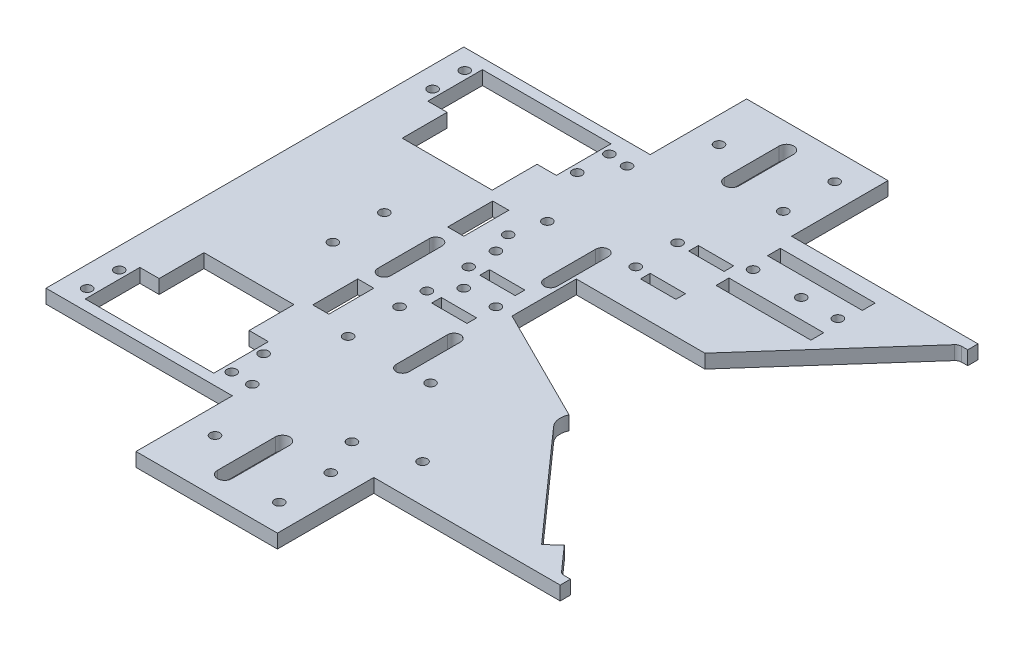
SolidWorks part; units mm, degrees
material "Acrylic (Medium-high impact)"
ref_plane "Front Plane" through (0, 0, 0) normal (0, 0, 1) x (1, 0, 0)
ref_plane "Top Plane" through (0, 0, 0) normal (0, 1, 0) x (1, 0, 0)
ref_plane "Right Plane" through (0, 0, 0) normal (1, 0, 0) x (0, 0, -1)
sketch "Sketch2" plane through (0, 0, 0) normal (0, 1, 0) x (1, 0, 0)
  line L2 (0, 0) -> (0, 65)
  line L3 (0, 65) -> (58, 65)
  line L4 (160, 0) -> (160, 65)
  line L8 (0, 0) -> (160, 0)
  line L9 (102, 65) -> (160, 65)
  line L11 (102, 65) -> (102, 95)
  line L12 (58, 65) -> (58, 95)
  line L13 (58, 95) -> (102, 95)
  dimension "D1" = 65
  dimension "D2" = 160
  dimension "D3" = 44
  dimension "D4" = 30
extrude "Boss-Extrude1" add sketch "Sketch2" along normal blind 4.3
mirror "Mirror1" about plane through (0, 4.3, 0) normal (0, 0, -1) of bodies 101
sketch "Sketch3" plane through (0, 4.3, 0) normal (0, 1, 0) x (1, 0, 0)
  line L0 (160, 61.8) -> (160, -61.8)
  line L1 (120.0126, 20) -> (157.1565, 61.8)
  line L3 (80.0126, 0) -> (80.0126, 20)
  line L4 (80.0126, 20) -> (120.0126, 20)
  line L12 (160, 65) -> (102, 65)
  line L13 (102, 65) -> (102, 95)
  line L15 (102, 95) -> (58, 95)
  line L16 (58, 65) -> (0, 65)
  line L17 (0, 65) -> (0, -65)
  line L18 (0, -65) -> (58, -65)
  line L20 (58, 95) -> (58, 65)
  line L22 (102, -65) -> (160, -65)
  line L23 (160, -65) -> (160, 65)
  line L36 (58, -65) -> (58, -95)
  line L38 (58, -95) -> (102, -95)
  line L39 (58, -95) -> (102, -95)
  line L40 (102, -95) -> (102, -65)
  line L42 (160, -61.8) -> (157.1556, -61.8)
  line L45 (160, 61.8) -> (157.1565, 61.8)
  line L48 (80.0126, 0) -> (120, -20)
  line L49 (120, -20) -> (157.1556, -61.8)
  line M24 (160, -65) -> (160, 65)
  dimension "D2" = 130
  dimension "D3" = 20
  dimension "D4" = 40
  dimension "D1" = 0
extrude "Cut-Extrude1" cut sketch "Sketch3" against normal blind 4.5 contours L48 L49 L1 L4 L3 M24 region at (132.7054, 4.3, -1.1594)
fillet "Fillet1" radius 2 2 edges at (157.1565, 2.15, -61.8) (157.1556, 2.15, 61.8)
ref_axis "Axis1" through (80, 4.3, 95) along (0, 0, -1)
sketch "Sketch4" plane through (0, 4.3, 0) normal (0, 1, 0) x (1, 0, 0)
  line L0 (80, -95) -> (80, 95)
  line L1 (102, -95) -> (58, -95) construction
  line L2 (102, 95) -> (58, 95) construction
ref_plane "Plane2" through (0, 4.3, 0) normal (0, 1, 0) x (1, 0, 0)
sketch "Sketch6" plane through (0, 4.3, 0) normal (0, 1, 0) x (1, 0, 0)
  line L3 (9, -61.8) -> (49, -61.8)
  line L6 (29, -45.8) -> (29, -44.8)
  line L7 (9, -44.8) -> (15, -44.8)
  line L11 (43, -44.8) -> (43, -30.8418)
  line L12 (15, -44.8) -> (15, -30.8418)
  line L13 (15, -30.8418) -> (43, -30.8418)
  line L15 (0, 0) -> (80.0126, 0)
  line L16 (80.0126, 0) -> (120, -20) construction
  line L18 (9, 44.8) -> (15, 44.8)
  line L20 (15, 30.8418) -> (43, 30.8418)
  line L21 (15, 44.8) -> (15, 30.8418)
  line L22 (43, 44.8) -> (43, 30.8418)
  line L25 (15, -45.8) -> (15, -30.8418) construction
  line L27 (9, 61.8) -> (49, 61.8)
  line L30 (4, -61.8) -> (3, -61.8)
  line L31 (0, -61.8) -> (160, -61.8) construction
  line L32 (3, -61.8) -> (4, -61.8)
  line L33 (3, -44.8) -> (3, -62.8) construction
  line L34 (3, -62.8) -> (55, -62.8) construction
  line L35 (55, -44.8) -> (55, -62.8) construction
  line L36 (4, -61.8) -> (54, -61.8) construction
  line L37 (0, 61.8) -> (160, 61.8) construction
  line L38 (54, 61.8) -> (55, 61.8)
  line L39 (54, 61.8) -> (55, 61.8)
  line L40 (43, 44.8) -> (49, 44.8)
  line L41 (4, -45.8) -> (4, -61.8) construction
  line L42 (4, -45.8) -> (54, -45.8) construction
  line L43 (43, -44.8) -> (49, -44.8)
  line L44 (3, -44.8) -> (55, -44.8) construction
  line L45 (29, -45.8) -> (29, -30.8418) construction
  line L46 (43, -45.8) -> (43, -30.8418) construction
  line L47 (54, -45.8) -> (54, -61.8) construction
  line L48 (9, -61.8) -> (49, -61.8)
  line L52 (9, 61.8) -> (9, 44.8)
  line L53 (55, 61.8) -> (54, 61.8)
  line L56 (49, 61.8) -> (49, 44.8)
  line L59 (3, -61.8) -> (4, -61.8)
  line L60 (9, -44.8) -> (9, -61.8)
  line L64 (49, -44.8) -> (49, -61.8)
  dimension "D4" = 1
  dimension "D5" = 14
  dimension "D6" = 14
extrude "Cut-Extrude2" cut sketch "Sketch6" against normal blind 10
sketch "Sketch8" plane through (0, 4.3, 0) normal (0, 1, 0) x (1, 0, 0)
  circle A0 centre (6.5, 58.8) radius 1.5
  circle A1 centre (6.5, 48.8) radius 1.5
  circle A2 centre (51.5, 48.8) radius 1.5
  circle A3 centre (51.5, 58.8) radius 1.5
  circle A4 centre (6.5, -48.7) radius 1.5
  circle A5 centre (6.5, -58.7) radius 1.5
  circle A6 centre (51.5, -58.7) radius 1.5
  circle A7 centre (51.5, -48.8) radius 1.5
  dimension "D7" = 3
extrude "Cut-Extrude3" cut sketch "Sketch8" against normal blind 10
sketch "Sketch9" plane through (0, 0, 0) normal (0, -1, 0) x (1, 0, 0)
  line L0 (75.75, 69.4) -> (75.75, 87.4)
  line L1 (75.75, -87.4) -> (75.75, -70.4)
  line L2 (80.25, -87.4) -> (80.25, -70.4)
  line L4 (80.25, 69.4) -> (80.25, 87.4)
  circle A0 centre (94, 70.4) radius 1.5
  circle A1 centre (66, 78.4) radius 1.5
  circle A2 centre (66, -78.4) radius 1.5
  circle A3 centre (94, -86.4) radius 1.5
  circle A4 centre (94, 86.4) radius 1.5
  circle A5 centre (94, -70.4) radius 1.5
  arc A6 (75.75, -87.4) -> (80.25, -87.4) centre (78, -87.4) ccw
  arc A7 (80.25, -70.4) -> (75.75, -70.4) centre (78, -70.4) ccw
  arc A10 (75.75, 69.4) -> (80.25, 69.4) centre (78, 69.4) ccw
  arc A12 (80.25, 87.4) -> (75.75, 87.4) centre (78, 87.4) ccw
  dimension "D1" = 3
extrude "Cut-Extrude4" cut sketch "Sketch9" against normal blind 10
sketch "Sketch7" plane through (0, 4.3, 0) normal (0, 1, 0) x (1, 0, 0)
  line L0 (0, 0) -> (80.0126, 0)
  line L1 (0, 65) -> (0, -65) construction
  line L2 (80.0126, 0) -> (80.0126, 20) construction
  line L3 (80, -95) -> (80, 95) construction
  line L4 (64, -9) -> (75, -9)
  line L5 (64, -6) -> (75, -6)
  line L6 (64, -9) -> (64, -6)
  line L7 (75, -9) -> (75, -6)
  line L8 (64, -7.5) -> (75, -7.5)
  line L9 (64, 7.5) -> (75, 7.5)
  line L10 (75, 9) -> (75, 6)
  line L11 (64, 9) -> (64, 6)
  line L12 (64, 6) -> (75, 6)
  line L13 (64, 9) -> (75, 9)
  line L14 (89.9874, 30) -> (100.9874, 30)
  line L15 (89.9874, 33) -> (100.9874, 33)
  line L16 (89.9874, 30) -> (89.9874, 33)
  line L17 (100.9874, 30) -> (100.9874, 33)
  line L20 (100.9874, 48) -> (100.9874, 45)
  line L21 (89.9874, 48) -> (89.9874, 45)
  line L22 (89.9874, 45) -> (100.9874, 45)
  line L23 (89.9874, 48) -> (100.9874, 48)
  line L24 (80.0126, 20) -> (120.0126, 20) construction
  circle A0 centre (60.0126, -6.5) radius 1.5
  circle A1 centre (60.0126, 6.5) radius 1.5
  circle A2 centre (86, 32.5) radius 1.5
  circle A3 centre (86, 45.5) radius 1.5
  dimension "D1" = 3
  dimension "D8" = 3
  dimension "D2" = 6.5
  dimension "D3" = 20
  dimension "D6" = 11
  dimension "D4" = 5
  dimension "D5" = 3
  dimension "D7" = 7.5
  dimension "D9" = 11
  dimension "D10" = 3
  dimension "D11" = 12
  dimension "D12" = 13
  dimension "D13" = 10
  dimension "D14" = 3.9874
  dimension "D15" = 0.5
  dimension "D16" = 0.5
  dimension "D17" = 3.9874
  dimension "D18" = 6
  dimension "D19" = 11
sketch "Sketch10" plane through (0, 4.3, 0) normal (0, 1, 0) x (1, 0, 0)
  line L0 (120, -20) -> (156.5589, -61.1287) construction
  line L1 (123.3218, -23.737) -> (149.8964, -53.6334)
  line L2 (116.263, -23.3218) -> (146.1593, -56.9552)
  line L3 (149.8964, -53.6334) -> (146.1593, -56.9552)
  line L4 (120, -20) -> (156.5589, -61.1287) construction
  line L5 (116.263, -23.3218) -> (152.8218, -64.4505) construction
  arc A0 (123.3218, -23.737) -> (116.263, -23.3218) centre (120, -20) ccw
  dimension "D1" = 5
  dimension "D2" = 45
extrude "Cut-Extrude5" cut sketch "Sketch10" against normal blind 10
sketch "Sketch11" plane through (0, 0, 0) normal (0, -1, 0) x (1, 0, 0)
  line L0 (0, 0) -> (80.0126, 0) construction
  line L1 (80, 95) -> (80, -95) construction
  line L2 (80.0126, 0) -> (0, 0)
  line L4 (75, 31.0313) -> (75, 15.0313)
  line L6 (79, 31.0313) -> (79, 15.0313)
  line L7 (79, -31.0313) -> (79, -15.0313)
  line L8 (75, -31.0313) -> (75, -15.0313)
  circle A0 centre (60, 31) radius 1.5
  circle A1 centre (60, 15) radius 1.5
  arc A2 (75, 31.0313) -> (79, 31.0313) centre (77, 31.0313) cw
  arc A3 (75, 15.0313) -> (79, 15.0313) centre (77, 15.0313) ccw
  arc A4 (75, -15.0313) -> (79, -15.0313) centre (77, -15.0313) cw
  arc A5 (75, -31.0313) -> (79, -31.0313) centre (77, -31.0313) ccw
  circle A6 centre (60, -15) radius 1.5
  circle A7 centre (60, -31) radius 1.5
  dimension "D1" = 3
  dimension "D2" = 16
  dimension "D3" = 15
  dimension "D4" = 20
  dimension "D5" = 15
  dimension "D6" = 4
extrude "Cut-Extrude6" cut sketch "Sketch11" against normal blind 10 contours L4 A3 L6 A2 | L8 A5 L7 A4 | A7 | A0 | A1 | A6 region at (77, 0, 23.0313) region at (77, 0, -23.0313) region at (60, 0, -31)
sketch "Sketch12" plane through (0, 0, 0) normal (0, -1, 0) x (-1, 0, 0)
  line L0 (0, 0) -> (-80.0126, 0) construction
  line L3 (-50.2627, -8) -> (-50.2627, 8)
  line L4 (-50.2627, 0) -> (-46.2627, 0)
  line L5 (-46.2627, -8) -> (-46.2627, 8)
  line L6 (0, 0) -> (-46.2627, 0)
  line L7 (0, 65) -> (0, -65) construction
  line L8 (-160, -61.8) -> (0, -61.8) construction
  line L9 (-80.0126, 0) -> (-50.2627, 0)
  line L10 (-80.0126, 0) -> (-115.5281, -17.7634) construction
  line L11 (-80.0126, 0) -> (-80.0126, 20) construction
  line L12 (-58, -65) -> (0, -65) construction
  line L13 (-58, 65) -> (0, 65) construction
  circle A0 centre (-32.2627, -8) radius 1.5
  circle A1 centre (-32.2627, 8) radius 1.5
  arc A2 (-46.2627, 8) -> (-50.2627, 8) centre (-48.2627, 8) ccw
  arc A3 (-50.2627, -8) -> (-46.2627, -8) centre (-48.2627, -8) ccw
  circle A5 centre (-32.2627, -8) radius 1.5 construction
  circle A6 centre (-32.2627, 8) radius 1.5 construction
  dimension "D1" = 3
  dimension "D8" = 8
  dimension "D9" = 8
  dimension "D2" = 8
  dimension "D3" = 14
  dimension "D4" = 4
  dimension "D5" = 61.8
  dimension "D6" = 65
  dimension "D7" = 65
extrude "Cut-Extrude7" cut sketch "Sketch12" against normal blind 10 contours A3 L5 L4 L3 | L4 L5 A2 L3 | A0 | A1 region at (48.2627, 0, 4.7958) region at (48.2627, 0, -4.7958) region at (32.2627, 0, 8) region at (32.2627, 0, -8)
extrude "Cut-Extrude8" cut sketch "Sketch7" against normal blind 9 contours A0 | L4 L7 L5 L6 | L12 L10 L13 L11 | A1 | L23 L20 L22 L21 | L15 L17 L14 L16 | A3 | A2
sketch "Sketch13" plane through (0, 4.3, 0) normal (0, 1, 0) x (1, 0, 0)
  line L0 (80.0126, 0) -> (59.0194, 0)
  line L1 (80, -95) -> (80, 95) construction
  circle A0 centre (65, 0) radius 1.5
  circle A1 centre (75, 0) radius 1.5
  dimension "D2" = 3
  dimension "D3" = 5
  dimension "D1" = 10
extrude "Cut-Extrude9" cut sketch "Sketch13" against normal blind 10 contours L0 A0 | L0 A0 | L0 A1 | L0 A1 region at (75, 4.3, 0.6366) region at (75, 4.3, -0.6366) region at (65, 4.3, 0.6366) region at (65, 4.3, -0.6366)
sketch "Sketch14" plane through (0, 4.3, 0) normal (0, 1, 0) x (1, 0, 0)
  circle A0 centre (57.5, 58.3) radius 1.5
  circle A2 centre (57.5, 21.3) radius 1.5
  circle A3 centre (85.37, -30.7129) radius 1.5
  circle A4 centre (105.301, -53.1351) radius 1.5
  dimension "D1" = 3
  dimension "D2" = 3
extrude "Cut-Extrude10" cut sketch "Sketch14" against normal blind 10
sketch "Sketch15" plane through (0, 4.3, 0) normal (0, 1, 0) x (1, 0, 0)
  line L1 (46, 28) -> (51, 28)
  line L2 (46, 28) -> (46, 14)
  line L3 (46, 14) -> (51, 14)
  line L4 (51, 28) -> (51, 14)
  line L6 (0, 65) -> (0, -65) construction
  line L7 (80.0126, 0) -> (53.7017, 0)
  line L8 (46, -14) -> (51, -14)
  line L9 (51, -28) -> (51, -14)
  line L10 (46, -28) -> (51, -28)
  line L11 (46, -28) -> (46, -14)
  arc A0 (50.2627, 8) -> (46.2627, 8) centre (48.2627, 8) ccw construction
  arc A1 (46.2627, -8) -> (50.2627, -8) centre (48.2627, -8) ccw construction
  dimension "D1" = 46
  dimension "D2" = 5
  dimension "D3" = 14
  dimension "D4" = 14
  dimension "D5" = 14
  dimension "D6" = 6
  dimension "D7" = 6
extrude "Cut-Extrude11" cut sketch "Sketch15" against normal blind 10 contours L4 L1 L2 L3 | L11 L10 L9 L8 region at (48.5, 4.3, -21) region at (48.5, 4.3, 21)
sketch "Sketch16" plane through (0, 4.3, 0) normal (0, 1, 0) x (1, 0, 0)
  circle A0 centre (89, -58.8) radius 1.5
  circle A1 centre (58, -58.8) radius 1.5
  dimension "D1" = 3
extrude "Cut-Extrude12" cut sketch "Sketch16" against normal blind 10
ref_plane "Plane3" through (44.2426, 0, 0) normal (1, 0, 0) x (0, 0, -1)
sketch "Sketch17" plane through (44.2426, 0, 0) normal (1, 0, 0) x (0, 0, -1)
  line L4 (0, 0) -> (20, 0)
  line L5 (20, 0) -> (20, 4.3)
  line L6 (20, 4.3) -> (0, 4.3)
  line L7 (0, 4.3) -> (0, 0)
  line L8 (0, 0) -> (20, 0)
  line L9 (20, 0) -> (20, 4.3)
  line L10 (20, 4.3) -> (0, 4.3)
  line L11 (0, 4.3) -> (0, 0)
  circle A0 centre (-2.83, 16.28) radius 0.5
  point P6 (0, 2.15)
  dimension "D4" = 1
  dimension "D2" = 2.83
  dimension "D3" = 14.13
  dimension "D1" = 0
sketch "Sketch18" plane through (0, 4.3, 0) normal (0, 1, 0) x (1, 0, 0)
  line L0 (121.5, 50) -> (129.9, 50)
  line L1 (103.5, 60) -> (133, 60)
  line L2 (102, 65) -> (102, 95) construction
  line L3 (160, 65) -> (102, 65) construction
  line L4 (103.5, 60) -> (103.5, 56)
  line L5 (106.5, 50) -> (118.5, 50)
  line L6 (133, 60) -> (133, 56)
  line L7 (103.5, 60) -> (133, 60)
  line L8 (103.5, 60) -> (103.5, 56)
  line L9 (103.5, 56) -> (133, 56)
  line L10 (133, 60) -> (133, 56)
  line L11 (103.5, 44) -> (133, 44)
  line L12 (133, 40) -> (133, 44)
  line L13 (103.5, 40) -> (133, 40)
  line L14 (103.5, 40) -> (103.5, 44)
  circle A0 centre (105, 50) radius 1.5
  circle A1 centre (120, 50) radius 1.5
  circle A3 centre (131.4, 50) radius 1.5
  dimension "D1" = 3
  dimension "D6" = 3
  dimension "D2" = 15
  dimension "D3" = 29.5
  dimension "D4" = 3
  dimension "D5" = 15
  dimension "D7" = 26.4
  dimension "D8" = 4
  dimension "D9" = 6
extrude "Cut-Extrude13" cut sketch "Sketch18" against normal blind 10 contours L4 L9 L6 L1 | A0 | A1 | A3 | L14 L13 L12 L11 region at (131.4, 4.3, -50) region at (120, 4.3, -50) region at (105, 4.3, -50) region at (118.25, 4.3, -58) region at (118.25, 4.3, -42)
